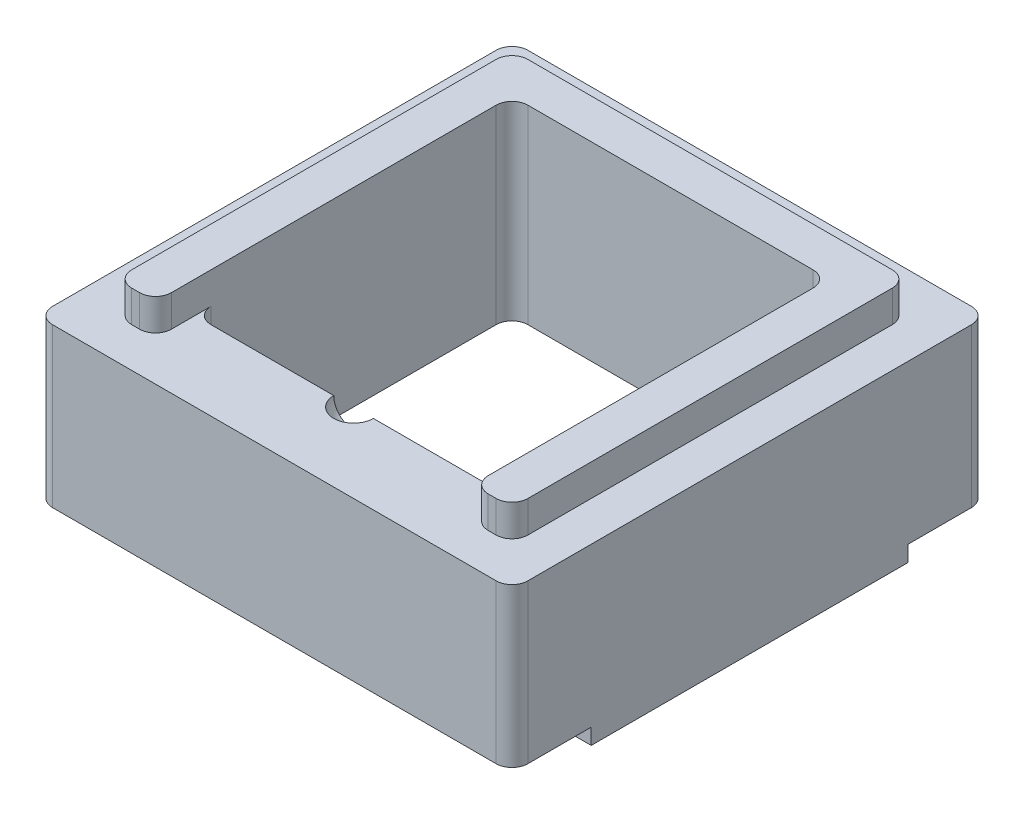
SolidWorks part; units mm, degrees
ref_plane "Front Plane" through (0, 0, 0) normal (0, 0, 1) x (1, 0, 0)
ref_plane "Top Plane" through (0, 0, 0) normal (0, 1, 0) x (1, 0, 0)
ref_plane "Right Plane" through (0, 0, 0) normal (1, 0, 0) x (0, 0, -1)
sketch "Sketch1" plane through (0, 0, 0) normal (0, 1, 0) x (1, 0, 0)
  line L1 (-12.5, -12.5) -> (12.5, -12.5)
  line L2 (-12.5, -12.5) -> (-12.5, 12.5)
  line L3 (-12.5, 12.5) -> (12.5, 12.5)
  line L4 (12.5, -12.5) -> (12.5, 12.5)
  line L5 (-12.5, -12.5) -> (12.5, 12.5) construction
  line L6 (-12.5, 12.5) -> (12.5, -12.5) construction
  line L7 (-10, -12.5) -> (10, -12.5)
  line L8 (-10, -12.5) -> (-10, 10)
  line L9 (-10, 10) -> (10, 10)
  line L10 (10, -12.5) -> (10, 10)
  point P0 (0, 0)
  point P10 (26.3749, -15)
  point P11 (-10, -15)
  point P12 (51.1431, -15)
  point P13 (0, -12.5)
  point P14 (0, -12.5)
  dimension "D1" = 2.5
  dimension "D2" = 25
  dimension "D3" = 2.5
extrude "Boss-Extrude1" add sketch "Sketch1" along normal blind 2 contours L10 L1 L4 L3 L2 L8 L9 region at (-12.1464, 0, 0)
sketch "Sketch3" plane through (0, 0, 0) normal (0, -1, 0) x (1, 0, 0)
  line L1 (-15, -15) -> (15, -15)
  line L2 (-15, -15) -> (-15, 15)
  line L3 (-15, 15) -> (15, 15)
  line L4 (15, -15) -> (15, 15)
  line L5 (-15, -15) -> (15, 15) construction
  line L6 (-15, 15) -> (15, -15) construction
  line L7 (-10, -10) -> (10, -10)
  line L8 (-10, -10) -> (-10, 10)
  line L9 (-10, 10) -> (10, 10)
  line L10 (10, -10) -> (10, 10)
  line L11 (-10, -10) -> (10, 10) construction
  line L12 (-10, 10) -> (10, -10) construction
  point P0 (0, 0)
  point P6 (0, 0)
  dimension "D1" = 30
  dimension "D2" = 5
extrude "Boss-Extrude2" add sketch "Sketch3" along normal blind 10 contours L2 L1 L4 L3 | L8 L7 L10 L9
sketch "Sketch4" plane through (0, -10, 0) normal (0, -1, 0) x (1, 0, 0)
  line L0 (0, -1000) -> (0, 49000) construction
  line L1 (-15, -10) -> (-13.5, -10)
  line L2 (-15, -10) -> (-15, 10)
  line L3 (-15, 10) -> (-13.5, 10)
  line L4 (-13.5, -10) -> (-13.5, 10)
  line L5 (13.5, -10) -> (13.5, 10)
  line L6 (15, 10) -> (13.5, 10)
  line L7 (15, -10) -> (15, 10)
  line L8 (15, -10) -> (13.5, -10)
  line L9 (-15, -15) -> (-15, 15) construction
  line L10 (-15, 15) -> (15, 15) construction
  dimension "D1" = 20
  dimension "D2" = 1.5
  dimension "D3" = 5
extrude "Boss-Extrude3" add sketch "Sketch4" along normal blind 1
sketch "Sketch5" plane through (0, 0, 0) normal (1, 0, 0) x (0, 0, -1)
  line L3 (-1000, 0) -> (49000, 0) construction
  circle A0 centre (-10, 0) radius 1.25
  point P0 (-10.145, 0)
  point P4 (0, 0)
  dimension "D1" = 2.5
  dimension "D2" = 10
revolve "Cut-Revolve4" cut sketch "Sketch5" angle 360 about L3 region at (0, -0.5305, 10)
fillet "Fillet2" radius 1 14 edges at (-15, -5, 15) (15, -5, 15) (15, -5, -15) (-15, -5, -15) (-10, -4, -10) (-10, -5, 10) (10, -5, 10) (10, -4, -10) (-10, 1, 12.5) (12.5, 1, -12.5) (12.5, 1, 12.5) (10, 1, 12.5) (-12.5, 1, 12.5) (-12.5, 1, -12.5)
